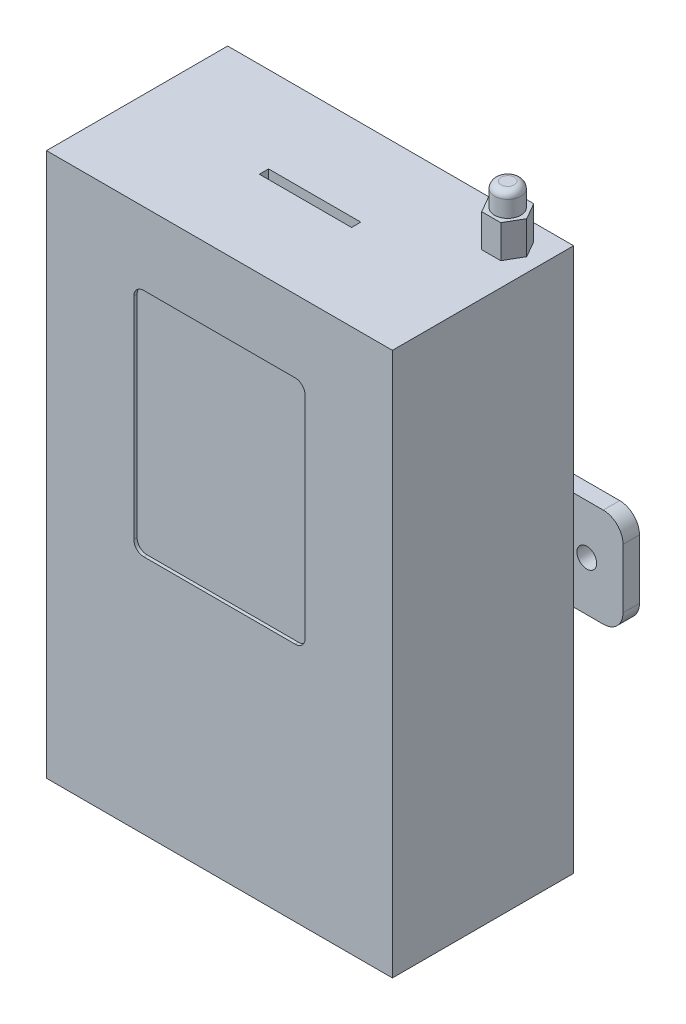
SolidWorks part; units mm, degrees
ref_plane "Płaszczyzna przednia" through (0, 0, 0) normal (0, 0, 1) x (1, 0, 0)
ref_plane "Płaszczyzna górna" through (0, 0, 0) normal (0, 1, 0) x (1, 0, 0)
ref_plane "Płaszczyzna prawa" through (0, 0, 0) normal (1, 0, 0) x (0, 0, -1)
sketch "Sketch1" plane through (0, 0, 0) normal (0, 1, 0) x (1, 0, 0)
  line L1 (-52.5, -27.5) -> (52.5, -27.5)
  line L2 (-52.5, -27.5) -> (-52.5, 27.5)
  line L3 (-52.5, 27.5) -> (52.5, 27.5)
  line L4 (52.5, -27.5) -> (52.5, 27.5)
  line L5 (-52.5, -27.5) -> (52.5, 27.5) construction
  line L6 (-52.5, 27.5) -> (52.5, -27.5) construction
  point P0 (0, 0)
  dimension "D1" = 105
  dimension "D2" = 55
extrude "Boss-Extrude1" add sketch "Sketch1" along normal blind 165
sketch "Sketch2" plane through (0, 165, 0) normal (0, 1, 0) x (1, 0, 0)
  line L1 (-14, -1.4) -> (14, -1.4)
  line L2 (-14, -1.4) -> (-14, 1.4)
  line L3 (-14, 1.4) -> (14, 1.4)
  line L4 (14, -1.4) -> (14, 1.4)
  line L5 (-14, -1.4) -> (14, 1.4) construction
  line L6 (-14, 1.4) -> (14, -1.4) construction
  point P0 (0, 0)
  dimension "D1" = 28
  dimension "D2" = 2.8
extrude "Cut-Extrude1" cut sketch "Sketch2" against normal blind 50
sketch "Sketch3" plane through (0, 0, 0) normal (0, 1, 0) x (1, 0, 0)
  line L0 (52.5, 27.5) -> (-52.5, 27.5) construction
  line L1 (48.2735, 17.5) -> (45.3868, 22.5)
  line L2 (45.3868, 22.5) -> (39.6132, 22.5)
  line L3 (39.6132, 22.5) -> (36.7265, 17.5)
  line L4 (36.7265, 17.5) -> (39.6132, 12.5)
  line L5 (39.6132, 12.5) -> (45.3868, 12.5)
  line L6 (45.3868, 12.5) -> (48.2735, 17.5)
  line L7 (52.5, -27.5) -> (52.5, 27.5) construction
  circle A0 centre (42.5, 17.5) radius 5 construction
  dimension "D1" = 10
  dimension "D2" = 10
  dimension "D3" = 10
extrude "Boss-Extrude2" add sketch "Sketch3" along normal blind 10 from surface starting at face at (0, 165, 0)
sketch "Sketch4" plane through (0, 175, 0) normal (0, 1, 0) x (1, 0, 0)
  line L0 (36.7265, 17.5) -> (48.2735, 17.5) construction
  line L1 (45.3868, 12.5) -> (48.2735, 17.5) construction
  circle A0 centre (42.5, 17.5) radius 4
  dimension "D1" = 8
extrude "Boss-Extrude3" add sketch "Sketch4" along normal blind 7
fillet "Fillet1" radius 2 1 edges at (42.5, 182, -13.5)
sketch "Sketch5" plane through (0, 0, 0) normal (0, 0, 1) x (1, 0, 0)
  line L0 (0, 0) -> (0, 165) construction
  line L1 (-52.5, 165) -> (52.5, 165) construction
  line L3 (-26, 73) -> (26, 73)
  line L4 (-26, 73) -> (-26, 143)
  line L5 (-26, 143) -> (26, 143)
  line L6 (26, 73) -> (26, 143)
  line L7 (-26, 73) -> (26, 143) construction
  line L8 (-26, 143) -> (26, 73) construction
  point P5 (0, 108)
  dimension "D1" = 70
  dimension "D2" = 52
  dimension "D3" = 22
extrude "Cut-Extrude2" cut sketch "Sketch5" against normal blind 1 from surface starting at face at (0, 82.5, 27.5)
sketch "Sketch6" plane through (0, 0, 0) normal (0, -1, 0) x (-1, 0, 0)
  line L1 (-2.5, 5) -> (2.5, 5)
  line L2 (-2.5, 5) -> (-2.5, -5)
  line L3 (-2.5, -5) -> (2.5, -5)
  line L4 (2.5, 5) -> (2.5, -5)
  line L5 (-2.5, 5) -> (2.5, -5) construction
  line L6 (-2.5, -5) -> (2.5, 5) construction
  point P0 (0, 0)
  dimension "D1" = 5
  dimension "D2" = 10
extrude "Cut-Extrude3" cut sketch "Sketch6" against normal blind 1
fillet "Fillet2" radius 2.5 4 edges at (-2.5, 0.5, -5) (2.5, 0.5, -5) (2.5, 0.5, 5) (-2.5, 0.5, 5)
sketch "Sketch7" plane through (0, 0, 0) normal (0, 0, 1) x (1, 0, 0)
  line L0 (0, 0) -> (0, 98.9399) construction
  line L1 (-67.5, 85) -> (67.5, 85) construction
  line L2 (-67.5, 70) -> (67.5, 70)
  line L3 (-67.5, 70) -> (-67.5, 100)
  line L4 (-67.5, 100) -> (67.5, 100)
  line L5 (67.5, 70) -> (67.5, 100)
  line L6 (-67.5, 70) -> (67.5, 100) construction
  line L7 (-67.5, 100) -> (67.5, 70) construction
  line L8 (-52.5, 165) -> (52.5, 165) construction
  circle A0 centre (-56.5, 85) radius 3
  circle A1 centre (56.5, 85) radius 3
  point P1 (0, 85)
  dimension "D5" = 6
  dimension "D6" = 6
  dimension "D1" = 56.5
  dimension "D2" = 113
  dimension "D3" = 135
  dimension "D4" = 30
  dimension "D7" = 65
extrude "Boss-Extrude4" add sketch "Sketch7" against normal blind 5 from surface starting at face at (0, 82.5, -27.5)
fillet "Fillet3" radius 6 4 edges at (-67.5, 70, -30) (-67.5, 100, -30) (67.5, 70, -30) (67.5, 100, -30)
fillet "Fillet4" radius 3 4 edges at (26, 143, 27) (-26, 143, 27) (-26, 73, 27) (26, 73, 27)
